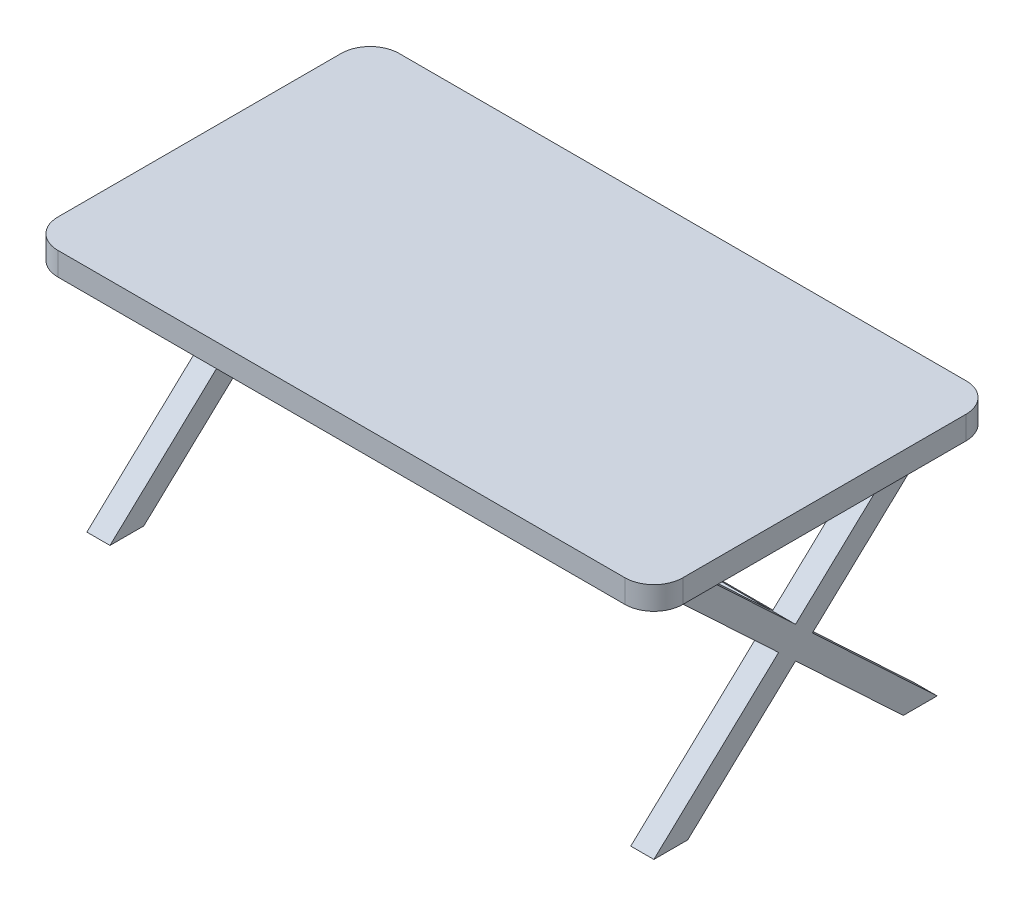
SolidWorks part; units mm, degrees
ref_plane "Front Plane" through (0, 0, 0) normal (0, 0, 1) x (1, 0, 0)
ref_plane "Top Plane" through (0, 0, 0) normal (0, 1, 0) x (1, 0, 0)
ref_plane "Right Plane" through (0, 0, 0) normal (1, 0, 0) x (0, 0, -1)
sketch "Sketch1" plane through (0, 0, 0) normal (1, 0, 0) x (0, 0, -1)
  line L0 (-400, -375) -> (400, 375) construction
  line L1 (-372.6424, -404.1815) -> (0, -54.8293)
  line L2 (-400, 375) -> (400, -375) construction
  line L3 (-489.6115, 404.1815) -> (-58.4846, 0)
  line L4 (-489.6115, -404.1815) -> (-58.4846, 0)
  line L5 (-372.6424, 404.1815) -> (0, 54.8293)
  line L6 (-489.6115, 404.1815) -> (-372.6424, 404.1815)
  line L7 (-489.6115, -404.1815) -> (-372.6424, -404.1815)
  line L8 (-372.6424, -404.1815) -> (427.3576, 345.8185) construction
  line L9 (-427.3576, 345.8185) -> (372.6424, -404.1815) construction
  line L10 (372.6424, 404.1815) -> (489.6115, 404.1815)
  line L11 (372.6424, -404.1815) -> (489.6115, -404.1815)
  line L12 (0, 54.8293) -> (372.6424, 404.1815)
  line L13 (58.4846, 0) -> (489.6115, 404.1815)
  line L14 (0, -54.8293) -> (372.6424, -404.1815)
  line L15 (58.4846, 0) -> (489.6115, -404.1815)
  point P0 (0, 0)
  dimension "D1" = 750
  dimension "D2" = 750
  dimension "D3" = 800
  dimension "D4" = 800
  dimension "D5" = 40
extrude "Boss-Extrude1" add sketch "Sketch1" along normal blind 80
ref_plane "Plane1" through (980, 0, 0) normal (1, 0, 0) x (0, 0, -1)
mirror "Mirror2" about plane through (980, 0, 0) normal (1, 0, 0) of bodies 101
sketch "Sketch2" plane through (0, 404.1815, 0) normal (0, 1, 0) x (1, 0, 0)
  line L0 (80, 489.6115) -> (0, 489.6115) construction
  line L1 (0, 372.6424) -> (150, 372.6424)
  line L2 (0, 372.6424) -> (0, 489.6115)
  line L3 (0, 489.6115) -> (150, 489.6115)
  line L4 (150, 372.6424) -> (150, 489.6115)
  circle A0 centre (115, 459.6115) radius 5
  circle A1 centre (115, 430.6424) radius 5
  circle A2 centre (115, 402.6424) radius 5
  dimension "D2" = 10
  dimension "D3" = 10
  dimension "D4" = 10
  dimension "D1" = 150
  dimension "D5" = 35
  dimension "D6" = 35
  dimension "D7" = 35
  dimension "D8" = 30
  dimension "D9" = 30
  dimension "D10" = 28
base flange "Base-Flange1" sketch "Sketch2" thickness 5 reverse thickness direction yes parameters "D1"=1.5
mirror "Mirror3" about plane through (980, 0, 0) normal (1, 0, 0) of bodies 103
mirror "Mirror4" about plane through (0, 0, 0) normal (0, 0, 1) of bodies 104 103
sketch "Sketch13" plane through (1960, 0, 0) normal (1, 0, 0) x (0, 0, -1)
  line L0 (0, 54.8293) -> (-58.4846, 0)
  line L1 (-58.4846, 0) -> (0, -54.8293)
  line L2 (0, -54.8293) -> (58.4846, 0)
  line L3 (58.4846, 0) -> (0, 54.8293)
extrude "Boss-Extrude2" add sketch "Sketch13" against normal up to surface (1800 mm away) from offset 80 up to face at (80, 0, 0) offset against normal yes
sketch "Sketch14" plane through (0, 409.1815, 0) normal (0, 1, 0) x (1, 0, 0)
  line L0 (0, 0) -> (0, -372.6424) construction
  line L1 (0, 589.6115) -> (1960, 589.6115)
  line L2 (-100, 489.6115) -> (-100, -489.6115)
  line L3 (0, -589.6115) -> (1960, -589.6115)
  line L4 (2060, 489.6115) -> (2060, -489.6115)
  line L5 (1960, 489.6115) -> (1960, 372.6424) construction
  line L6 (1810, -489.6115) -> (1960, -489.6115) construction
  line L7 (1810, 489.6115) -> (1960, 489.6115) construction
  arc A0 (1960, 589.6115) -> (2060, 489.6115) centre (1960, 489.6115) cw
  arc A1 (1960, -589.6115) -> (2060, -489.6115) centre (1960, -489.6115) ccw
  arc A2 (-100, -489.6115) -> (0, -589.6115) centre (0, -489.6115) ccw
  arc A3 (0, 589.6115) -> (-100, 489.6115) centre (0, 489.6115) ccw
  dimension "D5" = 100
  dimension "D1" = 100
  dimension "D2" = 100
  dimension "D3" = 100
  dimension "D4" = 100
extrude "Boss-Extrude3" add sketch "Sketch14" along normal blind 80 separate body
sketch "Bend-Lines1" [suppressed] plane through (0, 0, 0) normal (0, 1, 0) x (1, 0, 0)
sketch "Bounding-Box1" [suppressed] plane through (0, 0, 0) normal (0, 1, 0) x (1, 0, 0)
sheet metal parameters "Sheet-Metal3" thickness 5 parameters "D1"=1.5
flat pattern "Flat-Pattern3" [suppressed]
sketch "Bend-Lines2" plane through (0, 0, 0) normal (0, 1, 0) x (1, 0, 0)
sketch3d "Bounding-Box2" [suppressed]
  line L0 (-150, 372.6424, 0) -> (0, 372.6424, 0) construction
  line L1 (-150, 489.6115, 0) -> (0, 489.6115, 0) construction
  line L2 (-150, 372.6424, 0) -> (-150, 489.6115, 0) construction
  line L3 (0, 372.6424, 0) -> (0, 489.6115, 0) construction
sheet metal parameters "Sheet-Metal4" thickness 5 parameters "D1"=1.5
flat pattern "Flat-Pattern4"
sketch "Bend-Lines3" plane through (0, 0, 0) normal (0, 1, 0) x (1, 0, 0)
sketch "Bounding-Box3" [suppressed] plane through (0, 0, 0) normal (0, 1, 0) x (1, 0, 0)
sheet metal parameters "Sheet-Metal5" thickness 5 parameters "D1"=1.5
flat pattern "Flat-Pattern5"
sketch "Bend-Lines4" plane through (0, 0, 0) normal (0, 1, 0) x (1, 0, 0)
sketch "Bounding-Box4" [suppressed] plane through (0, 0, 0) normal (0, 1, 0) x (1, 0, 0)
sheet metal parameters "Sheet-Metal6" thickness 5 parameters "D1"=1.5
flat pattern "Flat-Pattern6"
sketch "Bend-Lines5" plane through (0, 0, 0) normal (0, 1, 0) x (1, 0, 0)
sketch "Bounding-Box5" [suppressed] plane through (0, 0, 0) normal (0, 1, 0) x (1, 0, 0)
